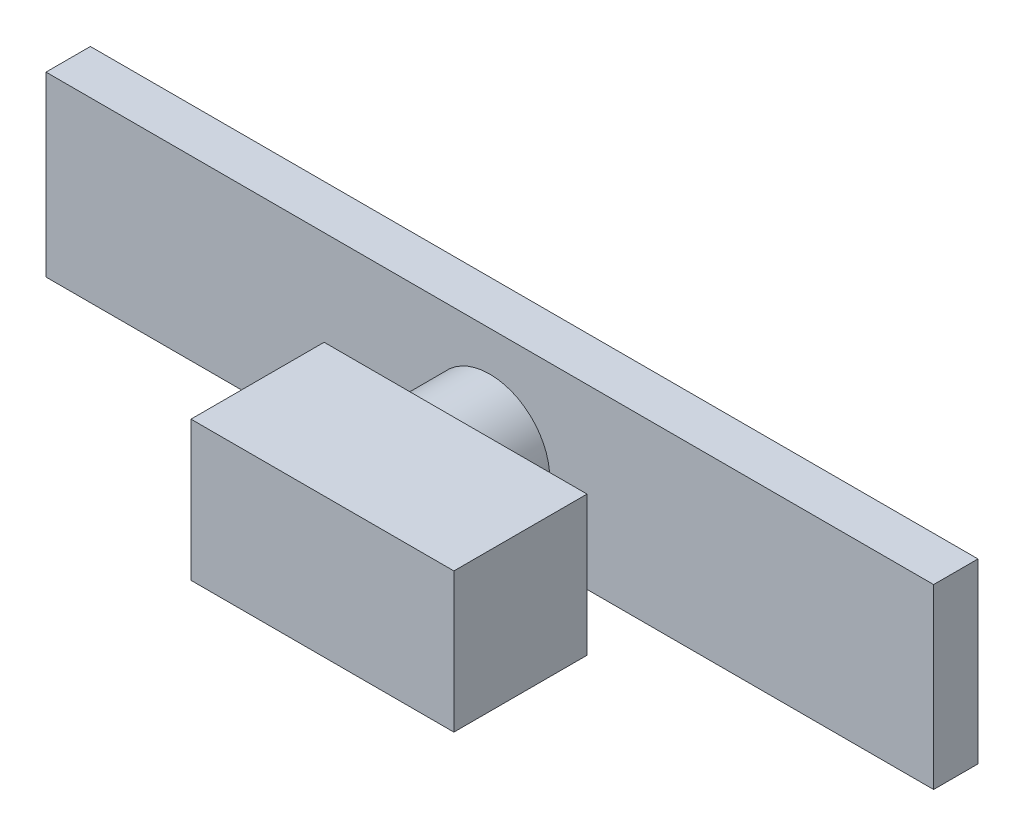
SolidWorks part; units mm, degrees
ref_plane "Front Plane" through (0, 0, 0) normal (0, 0, 1) x (1, 0, 0)
ref_plane "Top Plane" through (0, 0, 0) normal (0, 1, 0) x (1, 0, 0)
ref_plane "Right Plane" through (0, 0, 0) normal (1, 0, 0) x (0, 0, -1)
sketch "Sketch2" plane through (0, 0, 0) normal (0, 0, 1) x (1, 0, 0)
  line L1 (-47.8692, 21.2481) -> (206.1308, 21.2481)
  line L2 (-47.8692, 21.2481) -> (-47.8692, 8.5481)
  line L3 (-47.8692, 8.5481) -> (206.1308, 8.5481)
  line L4 (206.1308, 21.2481) -> (206.1308, 8.5481)
  dimension "D1" = 12.7
  dimension "D2" = 254
extrude "Boss-Extrude1" add sketch "Sketch2" along normal blind 50.8
sketch "Sketch3" plane through (0, 21.2481, 0) normal (0, 1, 0) x (1, 0, 0)
  circle A0 centre (79.1308, -28.4831) radius 17.1408
extrude "Boss-Extrude2" add sketch "Sketch3" along normal blind 19.05
sketch "Sketch4" plane through (0, 40.2981, 0) normal (0, 1, 0) x (1, 0, 0)
  line L1 (50.7675, -8.111) -> (126.0034, -8.111)
  line L2 (50.7675, -8.111) -> (50.7675, -48.0661)
  line L3 (50.7675, -48.0661) -> (126.0034, -48.0661)
  line L4 (126.0034, -8.111) -> (126.0034, -48.0661)
extrude "Boss-Extrude3" add sketch "Sketch4" along normal blind 38.1
scale "Scale2" scale about centroid uniform scaling yes scale factor 0.06
move or copy body "Body-Move/Copy1" bodies to move or copy 105 copy no rotation origin (0, 33.6669, 26.5501) rotation axis (1, 0, 0) rotation angle 90
move or copy body "Body-Move/Copy3" bodies to move or copy 106 copy no translate (-50.8, 0, -50.8)
scale "Scale5" scale about centroid uniform scaling yes scale factor 0.25
move or copy body "Body-Move/Copy9" bodies to move or copy 111 copy no translate (-50.8, 0, 0)
scale "Scale6" bodies to scale 121 scale about centroid uniform scaling yes scale factor 0.25
